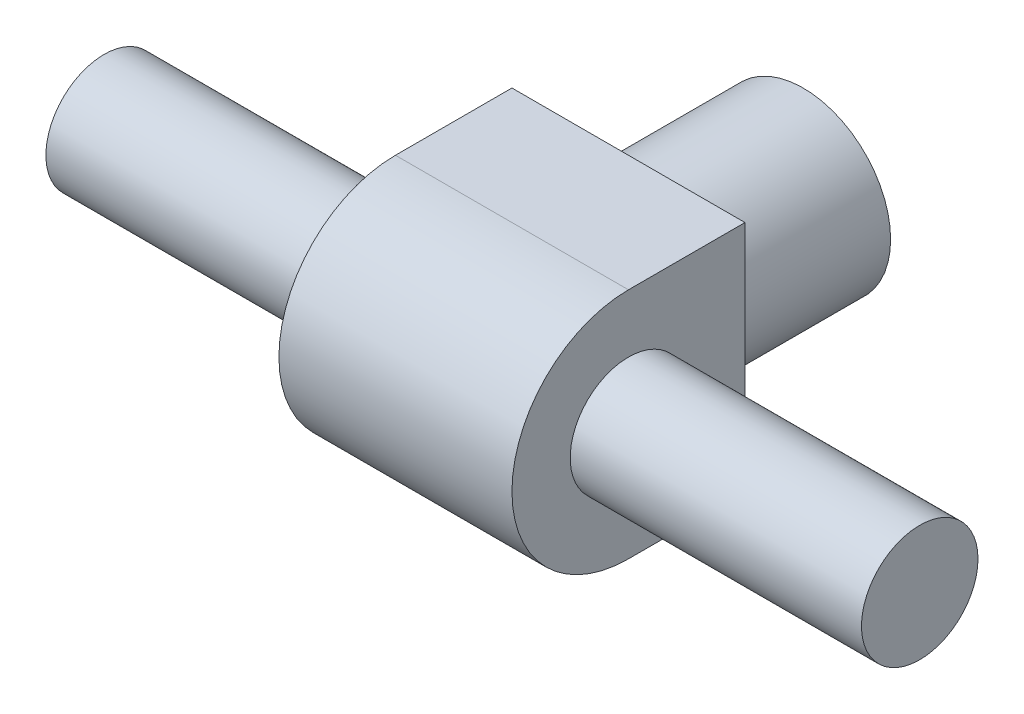
SolidWorks part; units mm, degrees
ref_plane "Спереди" through (0, 0, 0) normal (0, 0, 1) x (1, 0, 0)
ref_plane "Сверху" through (0, 0, 0) normal (0, 1, 0) x (1, 0, 0)
ref_plane "Справа" through (0, 0, 0) normal (1, 0, 0) x (0, 0, -1)
sketch "Эскиз1" plane through (0, 0, 0) normal (0, 0, 1) x (1, 0, 0)
  circle A0 centre (0, 0) radius 7.5
  dimension "D1" = 15
extrude "Бобышка-Вытянуть1" add sketch "Эскиз1" along normal blind 15
ref_plane "Плоскость4" through (0, 0, 0) normal (1, 0, 0) x (0, 0, -1)
sketch "Эскиз2" plane through (0, 0, 0) normal (1, 0, 0) x (0, 0, -1)
  line L0 (-15, 7.5) -> (-15, -7.5) construction
  line L1 (-15, 10) -> (-25, 10)
  line L2 (-15, -10) -> (-15, 10)
  line L4 (-25, -10) -> (-15, -10)
  line L5 (-35, 0) -> (-15, 0) construction
  arc A0 (-25, 10) -> (-25, -10) centre (-25, 0) ccw
  point P5 (-15, 0)
  point P10 (-25, 0)
  point P11 (0, 0)
  point P12 (0, 0)
  point P13 (0, 0)
  dimension "D1" = 20
  dimension "D2" = 10
sketch "Эскиз3" plane through (0, 0, 0) normal (1, 0, 0) x (0, 0, -1)
  circle A1 centre (-25, 0) radius 5
  point P0 (-25, 0)
  dimension "D1" = 10
extrude "Бобышка-Вытянуть2" add sketch "Эскиз2" along normal blind 10 and the other way blind 10
extrude "Бобышка-Вытянуть3" add sketch "Эскиз3" along normal blind 35 and the other way blind 35
sketch "Эскиз4" plane through (0, 0, 0) normal (1, 0, 0) x (0, 0, -1)
  point P0 (-25, 0)
  point P3 (0, 0)
